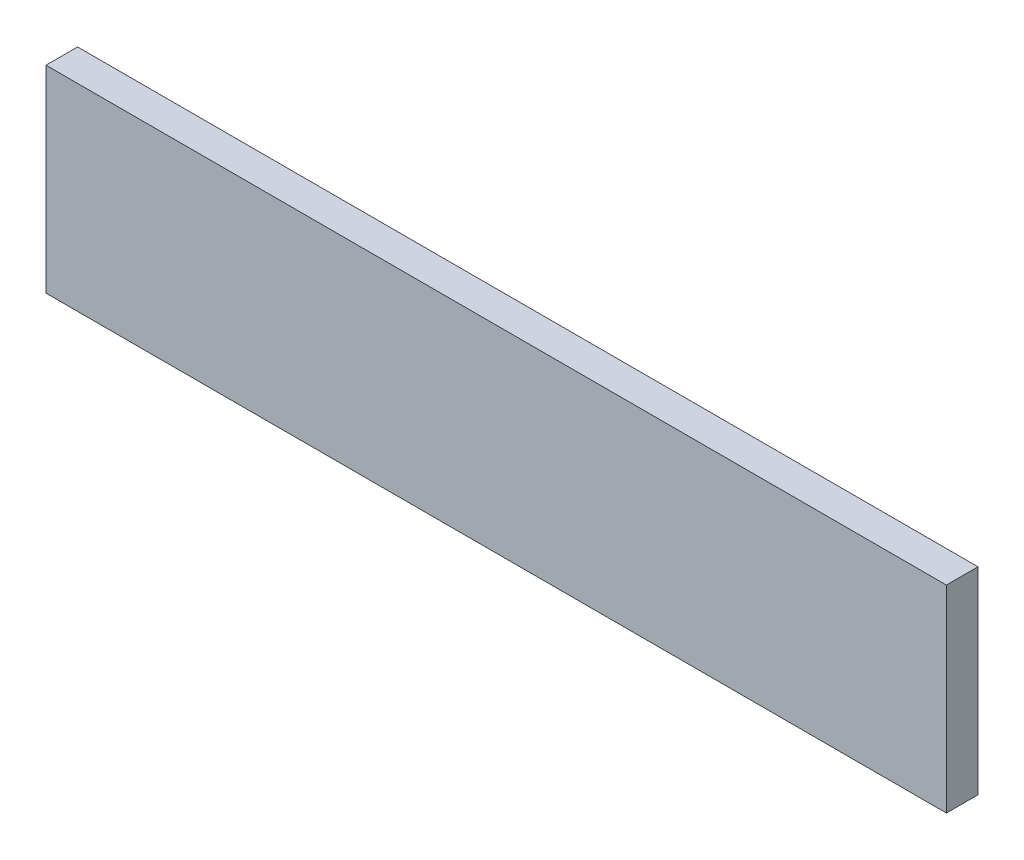
SolidWorks part; units mm, degrees
ref_plane "Ön Düzlem" through (0, 0, 0) normal (0, 0, 1) x (1, 0, 0)
ref_plane "Üst Düzlem" through (0, 0, 0) normal (0, 1, 0) x (1, 0, 0)
ref_plane "Sağ Düzlem" through (0, 0, 0) normal (1, 0, 0) x (0, 0, -1)
sketch "Çizim1" plane through (0, 0, 0) normal (0, 0, 1) x (1, 0, 0)
  line L1 (0, 0) -> (1140, 0)
  line L2 (0, 0) -> (0, -250)
  line L3 (0, -250) -> (1140, -250)
  line L4 (1140, 0) -> (1140, -250)
  dimension "D1" = 1140
  dimension "D2" = 250
base flange "Taban-Flanş1" sketch "Çizim1" thickness 40 reverse thickness direction no parameters "D1"=5
sketch "Büküm-Çizgileri1" [suppressed] plane through (0, 0, 0) normal (0, 1, 0) x (1, 0, 0)
sketch "Sınırlandırma-Kutusu1" [suppressed] plane through (0, 0, 0) normal (0, 1, 0) x (1, 0, 0)
sheet metal parameters "Sac-Levha1" thickness 40 parameters "D1"=5
flat pattern "Düz-Çoğaltma1" [suppressed]
sketch "Büküm-Çizgileri2" plane through (0, 0, 0) normal (0, 1, 0) x (1, 0, 0)
sketch3d "Sınırlandırma-Kutusu2" [suppressed]
  line L0 (0, -250, 0) -> (1140, -250, 0) construction
  line L1 (0, 0, 0) -> (1140, 0, 0) construction
  line L2 (0, -250, 0) -> (0, 0, 0) construction
  line L3 (1140, -250, 0) -> (1140, 0, 0) construction
